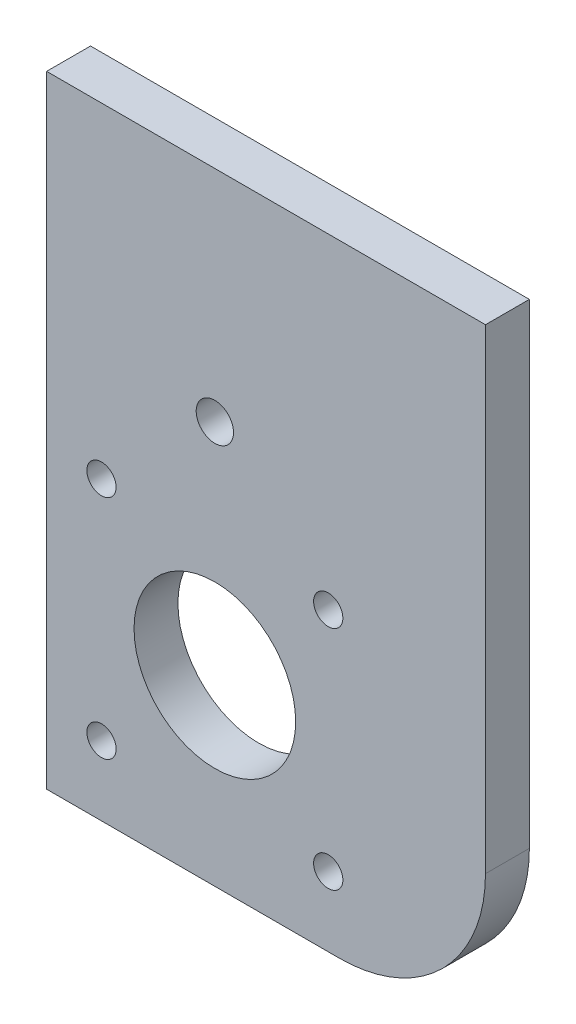
SolidWorks part; units mm, degrees
material "Клен"
ref_plane "Спереди" through (0, 0, 0) normal (0, 0, 1) x (1, 0, 0)
ref_plane "Сверху" through (0, 0, 0) normal (0, 1, 0) x (1, 0, 0)
ref_plane "Справа" through (0, 0, 0) normal (1, 0, 0) x (0, 0, -1)
sketch "Эскиз1" plane through (0, 0, 0) normal (0, 0, 1) x (1, 0, 0)
  line L0 (6, -293.8462) -> (6, -378.8462)
  line L1 (6, -293.8462) -> (6, -593.8462) construction
  line L7 (6, -293.8462) -> (66, -293.8462)
  line L11 (66, -293.8462) -> (66, -287.8462) construction
  line L12 (66, -293.8462) -> (66, -358.8462)
  line L14 (46, -378.8462) -> (6, -378.8462)
  arc A0 (66, -358.8462) -> (46, -378.8462) centre (46, -358.8462) cw
  circle A1 centre (29, -323.8462) radius 2.55
  dimension "D3" = 5.1
  dimension "D2" = 20
  dimension "D1" = 85
extrude "Бобышка-Вытянуть1" add sketch "Эскиз1" against normal blind 6 contours L0 L14 A0 L12 L7
sketch "Эскиз2" plane through (0, 0, 0) normal (0, 0, 1) x (1, 0, 0)
  line L0 (6, -293.8462) -> (6, -378.8462) construction
  line L2 (29, -353.8462) -> (29, -402.3555) construction
  line L3 (29, -353.8462) -> (54.8419, -353.8462) construction
  line L5 (6, -293.8462) -> (66, -293.8462) construction
  circle A0 centre (29, -353.8462) radius 11.05
  circle A1 centre (44.5, -369.3462) radius 2
  circle A2 centre (13.5, -369.3462) radius 2
  circle A3 centre (13.5, -338.3462) radius 2
  circle A4 centre (44.5, -338.3462) radius 2
  circle A5 centre (29, -323.8462) radius 2.55
  dimension "D2" = 22.1
  dimension "D3" = 4
  dimension "D6" = 5.1
  dimension "D1" = 60
  dimension "D4" = 15.5
  dimension "D5" = 15.5
  dimension "D7" = 23
extrude "Вырез-Вытянуть1" cut sketch "Эскиз2" against normal through all
